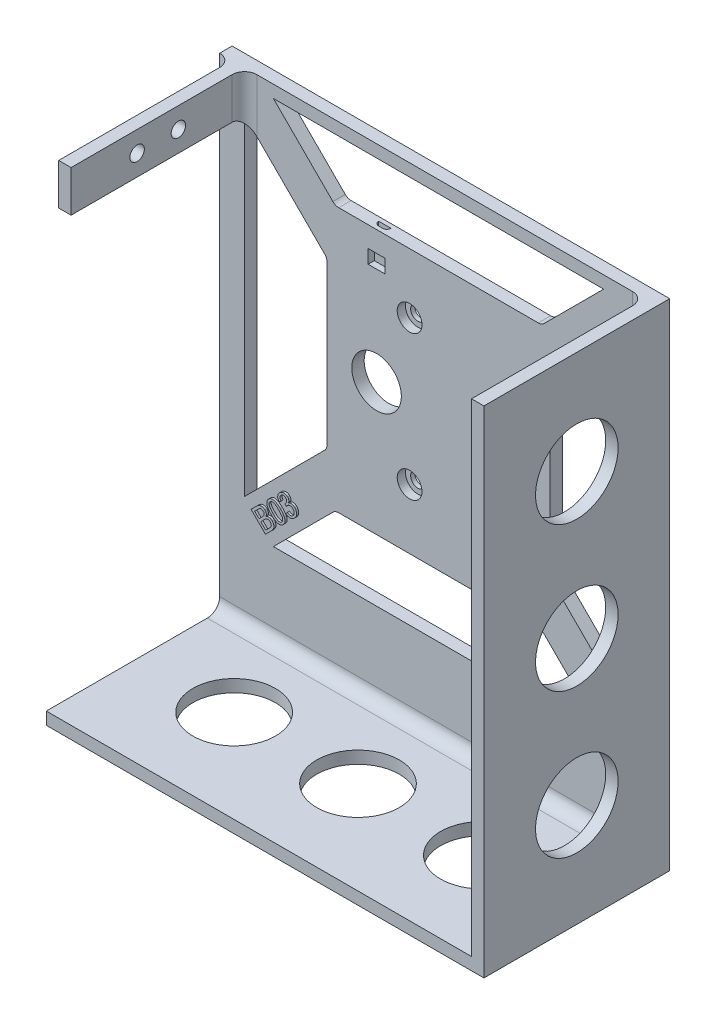
SolidWorks part; units mm, degrees
ref_plane "Front Plane" through (0, 0, 0) normal (0, 0, 1) x (1, 0, 0)
ref_plane "Top Plane" through (0, 0, 0) normal (0, 1, 0) x (1, 0, 0)
ref_plane "Right Plane" through (0, 0, 0) normal (1, 0, 0) x (0, 0, -1)
sketch "Sketch1" plane through (0, 0, 0) normal (0, 0, 1) x (1, 0, 0)
  line L1 (-50, 50) -> (50, 50)
  line L2 (-50, 50) -> (-50, -50)
  line L3 (-50, -50) -> (50, -50)
  line L4 (50, 50) -> (50, -50)
  line L5 (-50, 50) -> (50, -50) construction
  line L6 (-50, -50) -> (50, 50) construction
  line L7 (-47, 40) -> (-27, 20)
  line L8 (-27, 20) -> (-27, -20)
  line L9 (-27, -20) -> (-47, -40)
  line L11 (-47, 40) -> (-47, -40)
  line L12 (0, -50) -> (0, 50) construction
  line L13 (47, 40) -> (27, 20)
  line L14 (27, 20) -> (27, -20)
  line L15 (27, -20) -> (47, -40)
  line L16 (47, 40) -> (47, -40)
  line L17 (-40, 47) -> (40, 47)
  line L18 (40, 47) -> (25, 32)
  line L19 (25, 32) -> (-25, 32)
  line L20 (-25, 32) -> (-40, 47)
  line L21 (-50, 0) -> (50, 0) construction
  line L22 (25, -32) -> (-25, -32)
  line L23 (40, -47) -> (25, -32)
  line L24 (-40, -47) -> (40, -47)
  line L25 (-25, -32) -> (-40, -47)
  line L26 (50, -50) -> (50, -70)
  line L31 (50, 50) -> (53, 50)
  line L32 (50, 50) -> (50, -50)
  line L33 (50, -50) -> (53, -50)
  line L34 (53, 50) -> (53, -50)
  line L35 (-50, 50) -> (-53, 50)
  line L36 (-50, 50) -> (-50, -50)
  line L37 (-50, -50) -> (-53, -50)
  line L38 (-53, 50) -> (-53, -50)
  line L39 (-53, -50) -> (53, -50)
  line L40 (-53, -50) -> (-53, -70)
  line L41 (-53, -50) -> (53, -50)
  line L42 (-53, -70) -> (53, -70)
  line L43 (53, -50) -> (53, -70)
  circle A2 centre (-15, 0) radius 6
  circle A3 centre (-7, 17.5) radius 1.75
  circle A4 centre (-7, -17.5) radius 1.75
  point P0 (0, 0)
  point P6 (-47, 0)
  point P8 (-50, 0)
  point P23 (0, 47)
  dimension "D16" = 12
  dimension "D14" = 3.5
  dimension "D1" = 100
  dimension "D2" = 100
  dimension "D3" = 80
  dimension "D4" = 45
  dimension "D5" = 20
  dimension "D6" = 3
  dimension "D7" = 3
  dimension "D8" = 45
  dimension "D9" = 80
  dimension "D10" = 15
  dimension "D11" = 3
  dimension "D13" = 17.5
  dimension "D12" = 35
  dimension "D15" = 8
  dimension "D17" = 45
  dimension "D18" = 45
  dimension "D19" = 3
  dimension "D20" = 20
extrude "Base" add sketch "Sketch1" along normal blind 3 contours L1 L34 L16 L3 L4 | L40 L39 L43 L42 | L36 L35 L38 L37 | L32 L31 L34 L33 region at (0.3319, 0, 0)
sketch "Sketch6" plane through (0, 0, 3) normal (0, 0, 1) x (1, 0, 0)
  line L0 (40, 47) -> (47, 40) construction
  line L1 (-47, -40) -> (-40, -47) construction
  line L2 (-41.7678, -45.2322) -> (45.2322, 41.7678) construction
  line L3 (47, 40) -> (27, 20) construction
  text T0 "B03" font "Century Gothic" height 5
  dimension "D1" = 2.5
extrude "Revision" add sketch "Sketch6" along normal blind 0.5
sketch "Sketch3" plane through (0, 0, 3) normal (0, 0, 1) x (1, 0, 0)
  circle A0 centre (-7, 17.5) radius 3
  circle A1 centre (-7, -17.5) radius 3
  dimension "D1" = 6
  dimension "D2" = 6
extrude "Stepper_Holes" cut sketch "Sketch3" against normal blind 2
sketch "Sketch4" plane through (0, 0, 3) normal (0, 0, 1) x (1, 0, 0)
  line L0 (-15, 0) -> (-50.929, 0)
  line L1 (-50.929, 0) -> (-50.929, 40.2605)
  dimension "D1" = 35.929
  dimension "D2" = 40.2605
sketch "Sketch5" plane through (0, 0, 3) normal (0, 0, 1) x (1, 0, 0)
  line L0 (-50, 50) -> (-50, 40)
  line L2 (-50, 40) -> (-47, 40)
  line L6 (-47, 50) -> (-50, 50)
  line L7 (-47, 40) -> (-47, 50)
  line L8 (-53, 0) -> (0, 0) construction
  dimension "D1" = 10
  dimension "D2" = 3
extrude "Front_Tower" add sketch "Sketch5" along normal blind 42
sketch "Sketch8" plane through (-47, 0, 0) normal (1, 0, 0) x (0, 0, -1)
  line L1 (-45, 50) -> (-3, 50) construction
  line L2 (-24, 50) -> (-24, 40) construction
  line L3 (-45, 40) -> (-3, 40) construction
  circle A1 centre (-29, 45) radius 1.75
  circle A2 centre (-19, 45) radius 1.75
  point P13 (-24, 45)
  dimension "D1" = 3.5
  dimension "D2" = 5
extrude "Flip_Holder_Cut" cut sketch "Sketch8" against normal up to surface (3 mm away) up to face at (-50, 45, 24)
sketch "Sketch10" plane through (0, 0, 3) normal (0, 0, 1) x (1, 0, 0)
  line L7 (-53, -70) -> (53, -70)
  line L9 (53, -70) -> (53, 50)
  line L10 (53, 50) -> (50, 50)
  line L11 (-47, 50) -> (53, 50) construction
  line L12 (50, 50) -> (50, -67)
  line L13 (50, -67) -> (-53, -67)
  line L14 (-53, 50) -> (-53, -70) construction
  line L15 (-53, -67) -> (-53, -70)
  dimension "D1" = 3
extrude "Boss-Extrude1" add sketch "Sketch10" along normal blind 42
fillet "Fillet-2mm" radius 2 8 edges at (25, 32, 1.5) (-25, 32, 1.5) (-27, 20, 1.5) (27, 20, 1.5) (27, -20, 1.5) (-27, -20, 1.5) (25, -32, 1.5) (-25, -32, 1.5)
fillet "Fillet-3mm" radius 3 4 edges at (50, -8.5, 3) (-1.5, -67, 3) (-47, 45, 3) (-50, 45, 3)
sketch "Sketch11" plane through (53, 0, 0) normal (1, 0, 0) x (0, 0, -1)
  line L1 (-45, 50) -> (0, 50) construction
  line L2 (-45, -70) -> (-45, 50) construction
  circle A0 centre (-22.5, -10) radius 10
  circle A1 centre (-22.5, -45) radius 10
  circle A2 centre (-22.5, 25) radius 10
  point P5 (-22.5, 50)
  point P13 (-45, -10)
  dimension "D1" = 20
  dimension "D4" = 20
  dimension "D5" = 20
  dimension "D2" = 35
  dimension "D3" = 35
extrude "Back_Cut" cut sketch "Sketch11" against normal up to surface (3 mm away) up to face at (50, -8.5, 25.5)
sketch "Sketch12" plane through (0, -70, 0) normal (0, -1, 0) x (1, 0, 0)
  line L0 (-53, 45) -> (53, 45) construction
  line L1 (53, 45) -> (53, 0) construction
  line L2 (-53, 45) -> (-53, 0) construction
  circle A0 centre (0, 22.5) radius 10
  circle A1 centre (-30, 22.5) radius 10
  circle A2 centre (30, 22.5) radius 10
  point P11 (0, 45)
  point P15 (53, 22.5)
  point P19 (-53, 22.5)
  dimension "D1" = 20
  dimension "D2" = 20
  dimension "D3" = 20
  dimension "D4" = 30
  dimension "D5" = 30
extrude "Bottom_Cut" cut sketch "Sketch12" against normal up to surface (3 mm away) up to face at (-1.5, -67, 25.5)
sketch "Sensor" plane through (0, 0, 3) normal (0, 0, 1) x (1, 0, 0)
  line L1 (-17.05, 23.7) -> (-12.95, 23.7)
  line L2 (-17.05, 23.7) -> (-17.05, 27)
  line L3 (-17.05, 27) -> (-12.95, 27)
  line L4 (-12.95, 23.7) -> (-12.95, 27)
  line L10 (24.1716, 32) -> (-24.1716, 32) construction
  point P4 (-16.8295, 27)
  point P6 (-15, 23.7)
  point P8 (-15, 27)
  dimension "D1" = 4.1
  dimension "D2" = 3.3
  dimension "D3" = 5
  dimension "D4" = 9.1716
  dimension "D5" = 23.7
extrude "Sensor_Cut" cut sketch "Sensor" against normal blind 1.5
sketch "Sketch14" plane through (0, 32, 0) normal (0, 1, 0) x (1, 0, 0)
  line L1 (-16.5016, -1) -> (-13.5016, -1)
  line L2 (-16.5016, -1) -> (-16.5016, -2)
  line L3 (-16.5016, -2) -> (-13.5016, -2)
  line L4 (-13.5016, -1) -> (-13.5016, -2)
  line L6 (-24.1716, 0) -> (-24.1716, -3) construction
  point P6 (-24.1716, -1.5)
  point P7 (-16.5016, -1.5)
  point P8 (-15.0016, -2)
  dimension "D1" = 3
  dimension "D2" = 1
  dimension "D3" = 9.17
extrude "Sensor_Wires_Cut" cut sketch "Sketch14" against normal up to surface (5 mm away) up to face at (-15, 27, 2.25)
fillet "Fillet1" radius 1 2 edges at (-13.5016, 29.5, 2) (-16.5016, 29.5, 2)
equation "\"D3@Sketch1\"=\"D2@Sketch1\"*.8"
equation "\"D9@Sketch1\"=\"D1@Sketch1\"*.8"
equation "\"ServoDriverBoard_Width\"= 26.6mm"
equation "\"ServoDriverBoard_Length\"= 29.6mm"
equation "\"ServoDriverBoard_FromTop\"= 5mm"
equation "\"ServoDriverBoard_HoleSize\"= 3.3mm"
equation "\"Frame Size\"= 100mm"
equation "\"D1@Sketch1\"=\"Frame Size\""
equation "\"D2@Sketch3\"=\"D1@Sketch3\""
equation "\"Flip Y Offset\"= 36 * sin ( 3.6 )"
equation "\"Flip X Position\"= 36 * cos ( 3.6 )"
equation "\"Flip Length\"= 38mm"
equation "\"D1@Sketch4\"=\"Flip X Position\""
equation "\"D2@Sketch4\"=\"Flip Y Offset\"+\"Flip Length\""
equation "\"D2@Sketch11\"=\"D3@Sketch11\""
equation "\"D4@Sketch11\"=\"D1@Sketch11\""
equation "\"D5@Sketch11\"=\"D1@Sketch11\""
equation "\"D2@Sketch12\"=\"D1@Sketch12\""
equation "\"D3@Sketch12\"=\"D1@Sketch12\""
equation "\"D4@Sketch12\"=\"D5@Sketch12\""
